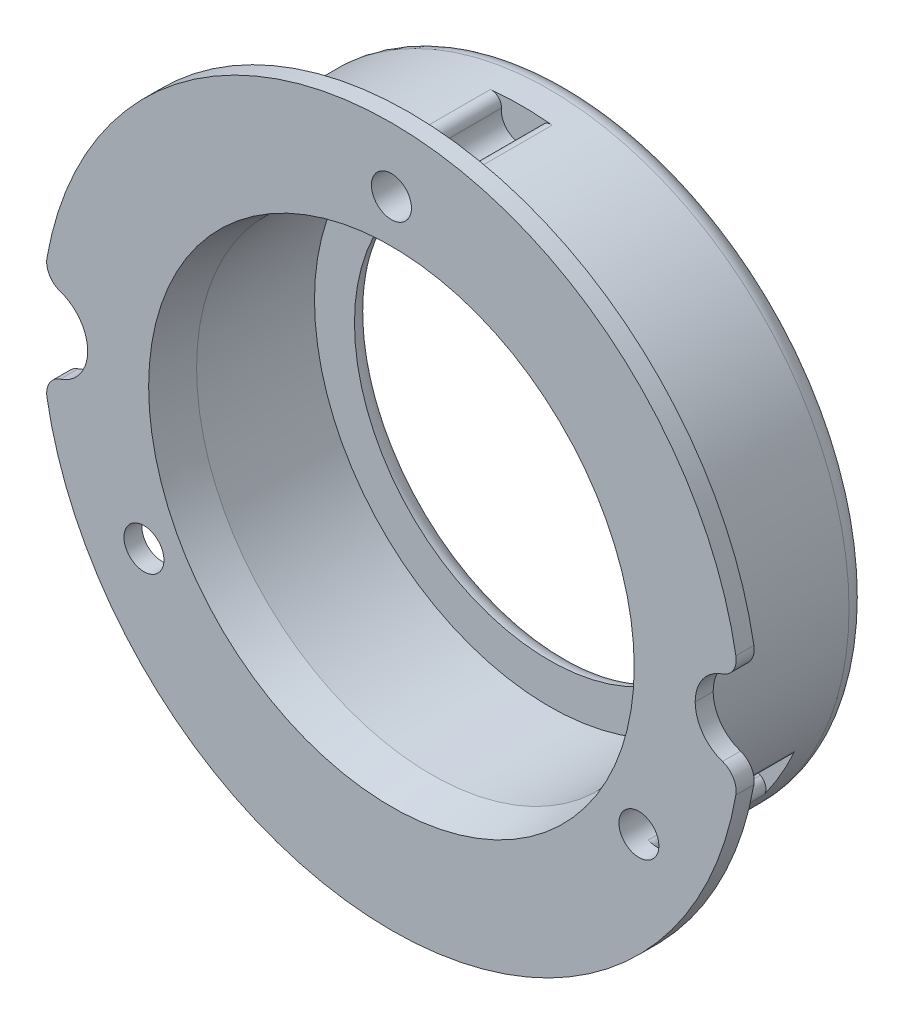
SolidWorks part; units mm, degrees
ref_plane "前视基准面" through (0, 0, 0) normal (0, 0, 1) x (1, 0, 0)
ref_plane "上视基准面" through (0, 0, 0) normal (0, 1, 0) x (1, 0, 0)
ref_plane "右视基准面" through (0, 0, 0) normal (1, 0, 0) x (0, 0, -1)
sketch "草图1" plane through (0, 0, 0) normal (0, 0, 1) x (1, 0, 0)
  circle A0 centre (0, 0) radius 15
  circle A1 centre (0, 0) radius 11.75
  dimension "D1" = 23.5
  dimension "D2" = 30
extrude "凸台-拉伸1" add sketch "草图1" along normal mid plane 8
sketch "草图2" plane through (0, 0, -4) normal (0, 0, -1) x (-1, 0, 0)
  circle A0 centre (0, 0) radius 11.75
  circle A1 centre (0, 0) radius 11.75 construction
  circle A2 centre (0, 0) radius 9.75
  dimension "D1" = 2
extrude "凸台-拉伸2" add sketch "草图2" against normal blind 1
fillet "圆角1" radius 1 1 edges at (15, 0, -4)
fillet "圆角2" radius 1 1 edges at (-9.75, 0, -4)
sketch "草图3" plane through (0, 0, 4) normal (0, 0, 1) x (1, 0, 0)
  circle A0 centre (0, 0) radius 11.75
  circle A1 centre (0, 0) radius 17.5
  circle A2 centre (0, 0) radius 11.75 construction
  dimension "D2" = 35
extrude "凸台-拉伸3" add sketch "草图3" along normal blind 0.9
sketch "草图4" plane through (0, 0, 4) normal (0, 0, -1) x (-1, 0, 0)
  line L0 (-23.6432, 0) -> (0, 0) construction
  line L1 (0, 0) -> (0, 22.776) construction
  line L3 (-20.0567, 2) -> (-15.0678, 2)
  line L4 (-20.0567, 2) -> (-20.0567, -2)
  line L5 (-20.0567, -2) -> (-15.0678, -2)
  arc A0 (-15.0678, 2) -> (-15.0678, -2) centre (0, 0) ccw
  dimension "D1" = 30.4
  dimension "D2" = 4
extrude "切除-拉伸1" cut sketch "草图4" against normal through all
mirror "镜向1" about plane through (0, 0, 0) normal (1, 0, 0) of "切除-拉伸1"
fillet "圆角3" radius 2 4 edges at (-15.0678, -2, 4.45) (-15.0678, 2, 4.45) (15.0678, -2, 4.45) (15.0678, 2, 4.45)
fillet "圆角4" radius 1 4 edges at (17.3853, 2, 4.45) (17.3853, -2, 4.45) (-17.3853, -2, 4.45) (-17.3853, 2, 4.45)
sketch "草图6" plane through (0, 0, 4.9) normal (0, 0, 1) x (1, 0, 0)
  line L0 (0, 20.0808) -> (0, 0) construction
  line L1 (0, 15.1) -> (3.1672, 15.1) construction
  circle A0 centre (0, 14.3) radius 1
  circle A1 centre (0, 0) radius 15 construction
  dimension "D1" = 2
  dimension "D2" = 0.2
extrude "切除-拉伸2" cut sketch "草图6" against normal blind 6.5
pattern_circular "阵列(圆周)2" count 3 every 120 about axis through (0, 0, 4) along (0, 0, -1) of "切除-拉伸2"
fillet "圆角6" radius 0.5 6 edges at (12.6093, -8.1243, 1.2) (13.3405, -6.8578, 1.2) (-12.6093, -8.1243, 1.2) (-13.3405, -6.8578, 1.2) (-0.7312, 14.9822, 1.2) (0.7312, 14.9822, 1.2)
chamfer "倒角1" distance 0.4 distance2 2 1 edges at (11.75, 0, 4.9) first distance on face at (-12.8842, -6.284, 4.9)
